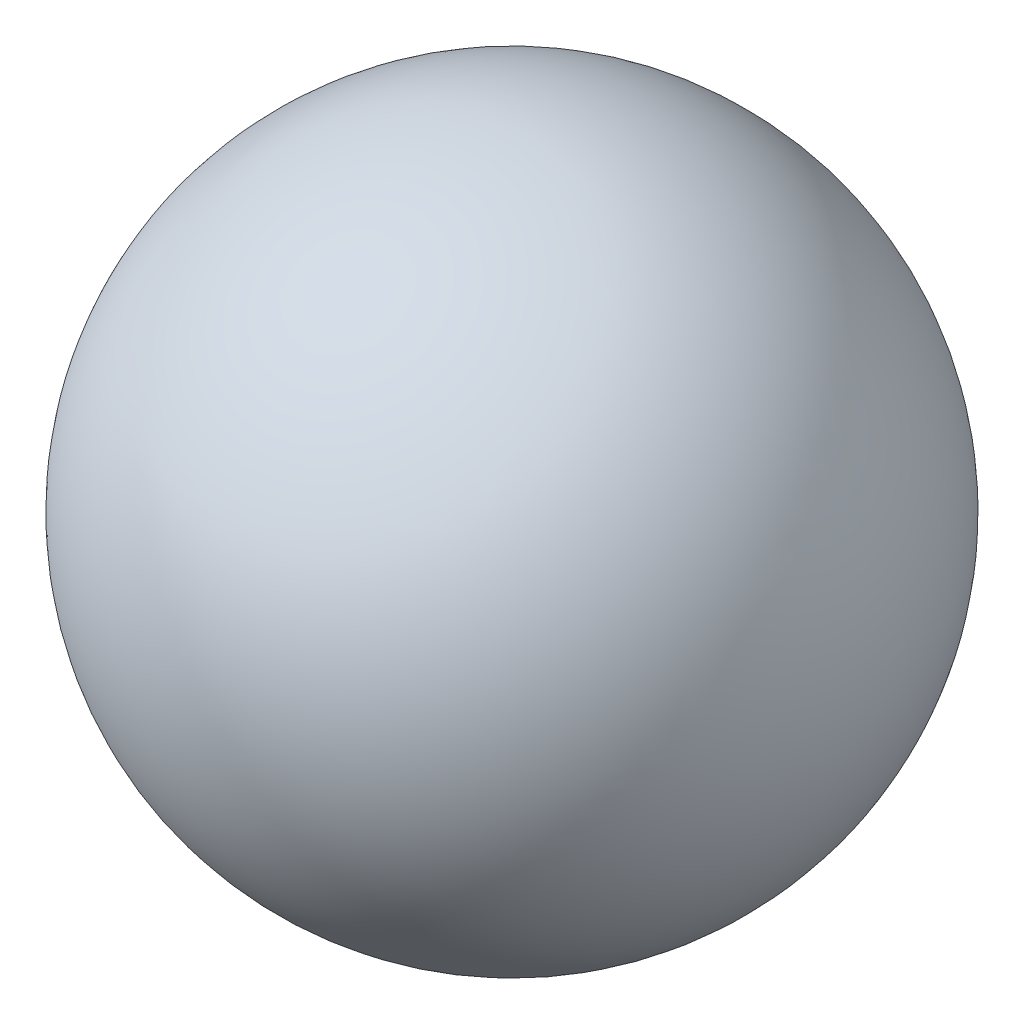
SolidWorks part; units mm, degrees
ref_plane "前视基准面" through (0, 0, 0) normal (0, 0, 1) x (1, 0, 0)
ref_plane "上视基准面" through (0, 0, 0) normal (0, 1, 0) x (1, 0, 0)
ref_plane "右视基准面" through (0, 0, 0) normal (1, 0, 0) x (0, 0, -1)
sketch "草图2" plane through (0, 0, 0) normal (0, 0, 1) x (1, 0, 0)
  line L0 (-21.25, 0) -> (21.25, 0)
  arc A0 (-21.25, 0) -> (21.25, 0) centre (0, 0) ccw
  dimension "D1" = 42.5
ref_axis "基准轴2" through (23.1, 0, 0) along (-1, 0, 0)
revolve "旋转4" add sketch "草图2" angle 360 about L0
